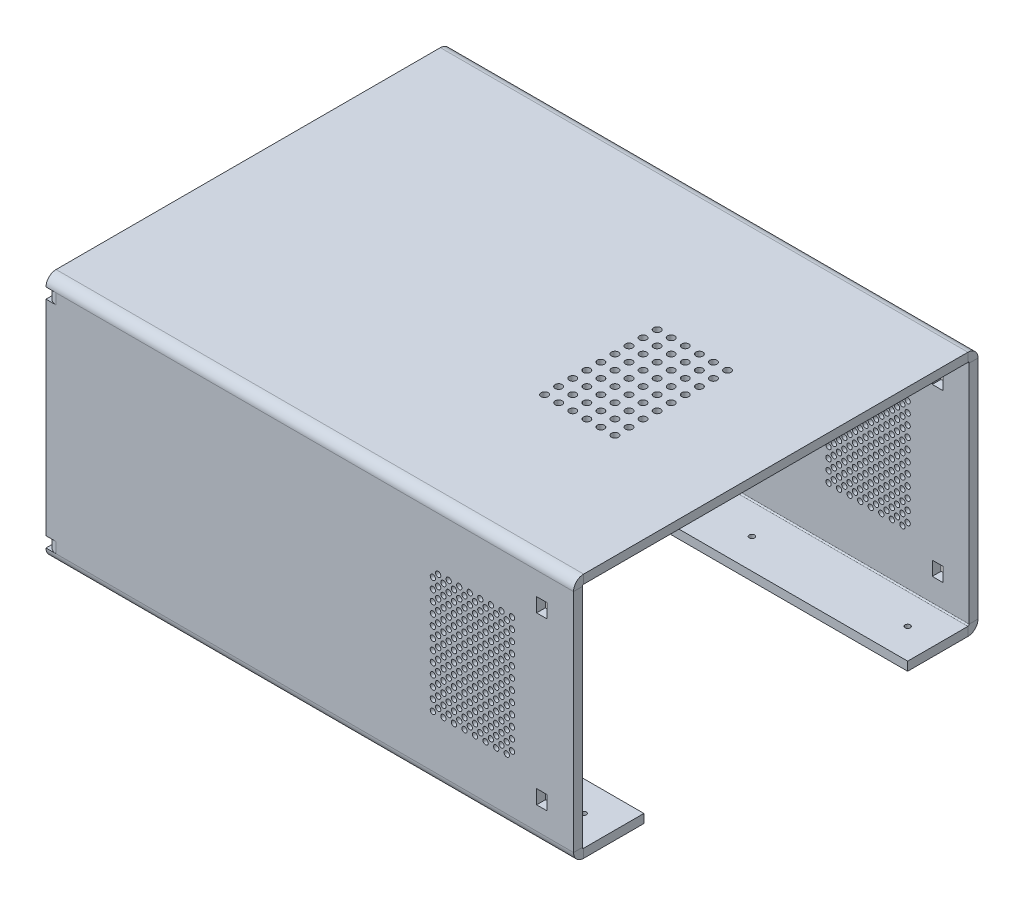
SolidWorks part; units mm, degrees
note: The reader was unsure of these and kept them because the rebuilt part matched: flange length of "Sides", "Bottom surfaces", "Edge-Flange4", "Edge-Flange5", "Edge-Flange6", "Edge-Flange7".
ref_plane "Front Plane" through (0, 0, 0) normal (0, 0, 1) x (1, 0, 0)
ref_plane "Top Plane" through (0, 0, 0) normal (0, 1, 0) x (1, 0, 0)
ref_plane "Right Plane" through (0, 0, 0) normal (1, 0, 0) x (0, 0, -1)
sketch "Sketch1" plane through (0, 0, 0) normal (0, 1, 0) x (1, 0, 0)
  line L1 (0, 0) -> (300, 0)
  line L2 (0, 0) -> (0, -220)
  line L3 (0, -220) -> (300, -220)
  line L4 (300, 0) -> (300, -220)
  dimension "D1" = 300
  dimension "D2" = 220
base flange "Top Surface" sketch "Sketch1" thickness 5 reverse thickness direction no parameters "D1"=0.7366
edge flange "Sides" sketch "Sketch10" flange profiles "Sketch10", "Sketch11" flange angle 90 flange length 140 flange position material outside bend radius 0.7366 thickness 5 relief rectangular parameters "D6"=10, "D8"=1
sketch "Sketch10" plane through (0, -5, 220) normal (0, 0, 1) x (-1, 0, 0)
  line L0 (0, 0) -> (-300, 0) construction
  line L1 (0, 0) -> (-300, 0)
  line L2 (-300, 0) -> (-300, 135)
  line L3 (-300, 135) -> (0, 135)
  line L4 (0, 135) -> (0, 0)
  dimension "D1" = 135
sketch "Sketch11" plane through (0, -5, 0) normal (0, 0, -1) x (1, 0, 0)
  line L0 (300, 0) -> (0, 0) construction
  line L1 (300, 0) -> (0, 0)
  line L2 (0, 0) -> (0, 135)
  line L3 (0, 135) -> (300, 135)
  line L4 (300, 135) -> (300, 0)
  line L7 (300, 135) -> (0, 135) construction
bend "EdgeBend1" bend radius 0.7366 bend angle 90 parameters "D5"=1
bend "EdgeBend2" bend radius 0.7366 bend angle 90 parameters "D5"=2
edge flange "Bottom surfaces" sketch "Sketch16" flange profiles "Sketch16", "Sketch17" flange angle 90 flange length 40 bend radius 0.7366 thickness 5 relief rectangular parameters "D6"=10, "D8"=1
sketch "Sketch16" plane through (0, -140, 220) normal (0, -1, 0) x (-1, 0, 0)
  line L2 (-300, 0) -> (-300, 35)
  line L3 (-300, 35) -> (0, 35)
  line L4 (0, 35) -> (0, 0)
  line L7 (0, 0) -> (-300, 0) construction
  line L8 (0, 0) -> (-300, 0)
sketch "Sketch17" plane through (0, -140, 0) normal (0, -1, 0) x (1, 0, 0)
  line L0 (300, 0) -> (0, 0) construction
  line L1 (300, 0) -> (0, 0)
  line L2 (0, 0) -> (0, 35)
  line L3 (0, 35) -> (300, 35)
  line L4 (300, 35) -> (300, 0)
bend "EdgeBend3" bend radius 0.7366 bend angle 90 parameters "D5"=3
bend "EdgeBend4" bend radius 0.7366 bend angle 90 parameters "D5"=4
sketch "Sketch27" plane through (0, -135, 0) normal (0, 1, 0) x (1, 0, 0)
  line L0 (17.1317, -17.8683) -> (17.1317, -202.1317) construction
  line L1 (17.1317, -202.1317) -> (105.7106, -202.1317) construction
  line L2 (105.7106, -202.1317) -> (194.2894, -202.1317) construction
  line L3 (194.2894, -202.1317) -> (282.8683, -202.1317) construction
  line L4 (282.8683, -202.1317) -> (282.8683, -17.8683) construction
  line L5 (282.8683, -17.8683) -> (194.2894, -17.8683) construction
  line L6 (194.2894, -17.8683) -> (105.7106, -17.8683) construction
  line L7 (105.7106, -17.8683) -> (105.7106, -202.1317) construction
  line L8 (17.1317, -17.8683) -> (105.7106, -17.8683) construction
  line L9 (194.2894, -17.8683) -> (194.2894, -202.1317) construction
  line L10 (17.1317, -17.8683) -> (0, -17.8683) construction
  line L11 (0, -35) -> (0, -0.7366) construction
  line L12 (282.8683, -17.8683) -> (300, -17.8683) construction
  line L13 (300, -0.7366) -> (300, -35) construction
  line L14 (17.1317, -17.8683) -> (17.1317, 5) construction
  line L15 (300, 5) -> (0, 5) construction
  line L16 (17.1317, -202.1317) -> (17.1317, -225) construction
  line L17 (0, -225) -> (300, -225) construction
  line L18 (17.1317, -202.1317) -> (0, -185) construction
  line L19 (17.1317, -202.1317) -> (0, -219.2634) construction
  line L20 (17.1317, -202.1317) -> (0, -202.1317) construction
  line L21 (0, -219.2634) -> (0, -185) construction
  line L22 (105.7106, -202.1317) -> (105.7106, -219.2634) construction
  line L23 (300, -219.2634) -> (0, -219.2634) construction
  circle A0 centre (17.1317, -17.8683) radius 1.5
  circle A1 centre (105.7106, -17.8683) radius 1.5
  circle A2 centre (194.2894, -17.8683) radius 1.5
  circle A3 centre (282.8683, -17.8683) radius 1.5
  circle A4 centre (17.1317, -202.1317) radius 1.5
  circle A5 centre (105.7106, -202.1317) radius 1.5
  circle A6 centre (194.2894, -202.1317) radius 1.5
  circle A7 centre (282.8683, -202.1317) radius 1.5
  dimension "D1" = 3
extrude "Screw Holes Bottom" cut sketch "Sketch27" against normal up to surface (5 mm away) normal cut yes up to face at (150, -140, 202.1317)
edge flange "Edge-Flange4" sketch "Sketch30" flange angle 90 flange length 11 flange position material inside bend radius 0.7366 thickness 5 relief none parameters "D6"=10
sketch "Sketch30" plane through (0, 0, 220) normal (-1, 0, 0) x (0, 1, 0)
  line L0 (-5.7366, 0) -> (-134.2634, 0) construction
  line L1 (-5.7366, 0) -> (-11.7366, 0)
  line L2 (-11.7366, 0) -> (-11.7366, 6)
  line L3 (-11.7366, 6) -> (-5.7366, 6)
  line L4 (-5.7366, 6) -> (-5.7366, 0)
  dimension "D1" = 6
  dimension "D2" = 6
bend "EdgeBend6" bend radius 0.7366 bend angle 90 parameters "D5"=5
edge flange "Edge-Flange5" sketch "Sketch33" flange angle 90 flange length 11 bend radius 0.7366 thickness 5 parameters "D6"=10
sketch "Sketch33" plane through (0, 0, 220) normal (-1, 0, 0) x (0, 1, 0)
  line L2 (-134.2634, 0) -> (-134.2634, 6)
  line L3 (-134.2634, 6) -> (-128.2634, 6)
  line L4 (-128.2634, 6) -> (-128.2634, 0)
  line L7 (-11.7366, 0) -> (-134.2634, 0) construction
  line L8 (-128.2634, 0) -> (-134.2634, 0)
  dimension "D1" = 6
  dimension "D2" = 6
bend "EdgeBend7" bend radius 0.7366 bend angle 90 parameters "D5"=6
edge flange "Edge-Flange6" sketch "Sketch36" flange angle 90 flange length 11 bend radius 0.7366 thickness 5 relief none parameters "D6"=10
sketch "Sketch36" plane through (0, 0, 0) normal (-1, 0, 0) x (0, -1, 0)
  line L0 (134.2634, 0) -> (5.7366, 0) construction
  line L1 (134.2634, 0) -> (128.2634, 0)
  line L2 (128.2634, 0) -> (128.2634, 6)
  line L3 (128.2634, 6) -> (134.2634, 6)
  line L4 (134.2634, 6) -> (134.2634, 0)
  dimension "D1" = 6
  dimension "D2" = 6
bend "EdgeBend8" bend radius 0.7366 bend angle 90 parameters "D5"=7
edge flange "Edge-Flange7" sketch "Sketch39" flange angle 90 flange length 11 bend radius 0.7366 thickness 5 relief none parameters "D6"=10
sketch "Sketch39" plane through (0, 0, 0) normal (-1, 0, 0) x (0, -1, 0)
  line L2 (5.7366, 0) -> (5.7366, 6)
  line L3 (5.7366, 6) -> (11.7366, 6)
  line L4 (11.7366, 6) -> (11.7366, 0)
  line L7 (128.2634, 0) -> (5.7366, 0) construction
  line L8 (11.7366, 0) -> (5.7366, 0)
  dimension "D1" = 6
  dimension "D2" = 6
bend "EdgeBend9" bend radius 0.7366 bend angle 90 parameters "D5"=8
sketch "Sketch40" plane through (0, 0, 0) normal (-1, 0, 0) x (0, 0, 1)
  line L0 (0.7366, -5.7366) -> (6, -11.7366) construction
  line L1 (6, -5.7366) -> (0.7366, -11.7366) construction
  line L4 (0.7366, -134.2634) -> (6, -128.2634) construction
  line L5 (0.7366, -128.2634) -> (6, -134.2634) construction
  line L6 (214, -128.2634) -> (219.2634, -134.2634) construction
  line L7 (219.2634, -128.2634) -> (214, -134.2634) construction
  line L8 (214, -134.2634) -> (219.2634, -134.2634) construction
  line L9 (214, -5.7366) -> (219.2634, -11.7366) construction
  line L10 (219.2634, -5.7366) -> (214, -11.7366) construction
  circle A0 centre (3.3683, -8.7366) radius 1.5
  circle A1 centre (3.3683, -131.2634) radius 1.5
  circle A2 centre (216.6317, -8.7366) radius 1.5
  circle A3 centre (216.6317, -131.2634) radius 1.5
  dimension "D1" = 3
extrude "Cut-Extrude3" cut sketch "Sketch40" against normal up to surface (5 mm away) normal cut yes up to face at (5, -8.7366, 3.3683)
sketch "Sketch42" plane through (0, 0, -5) normal (0, 0, -1) x (-1, 0, 0)
  line L0 (-265, -35.7366) -> (-265, -5.7366) construction
  line L1 (-300, -5.7366) -> (-5.7366, -5.7366) construction
  line L2 (-265, -35.7366) -> (-300, -35.7366) construction
  line L3 (-300, -5.7366) -> (-300, -134.2634) construction
  line L4 (-265, -35.7366) -> (-259, -35.7366) construction
  line L5 (-262, -38.7366) -> (-262, -35.7366) construction
  line L6 (-262, -38.7366) -> (-265, -35.7366) construction
  line L7 (-259, -35.7366) -> (-262, -38.7366) construction
  line L8 (-265, -41.7366) -> (-265, -11.7366) construction
  line L9 (-265, -53.7366) -> (-265, -23.7366) construction
  line L10 (-265, -53.7366) -> (-300, -53.7366) construction
  line L11 (-265, -53.7366) -> (-259, -53.7366) construction
  line L12 (-262, -56.7366) -> (-262, -53.7366) construction
  line L14 (-262, -56.7366) -> (-265, -53.7366) construction
  line L20 (-265, -47.7366) -> (-300, -47.7366) construction
  line L21 (-265, -41.7366) -> (-300, -41.7366) construction
  line L22 (-265, -47.7366) -> (-265, -17.7366) construction
  line L23 (-265, -41.7366) -> (-259, -41.7366) construction
  line L24 (-262, -44.7366) -> (-262, -41.7366) construction
  line L25 (-262, -44.7366) -> (-265, -41.7366) construction
  line L26 (-259, -41.7366) -> (-262, -44.7366) construction
  line L27 (-265, -47.7366) -> (-259, -47.7366) construction
  line L28 (-262, -50.7366) -> (-262, -47.7366) construction
  line L29 (-259, -47.7366) -> (-262, -50.7366) construction
  line L30 (-262, -50.7366) -> (-265, -47.7366) construction
  line L31 (-259, -53.7366) -> (-262, -56.7366) construction
  line L32 (-265, -59.7366) -> (-265, -29.7366) construction
  line L33 (-265, -59.7366) -> (-300, -59.7366) construction
  line L34 (-265, -59.7366) -> (-259, -59.7366) construction
  line L35 (-262, -62.7366) -> (-262, -59.7366) construction
  line L36 (-262, -62.7366) -> (-265, -59.7366) construction
  line L37 (-259, -59.7366) -> (-262, -62.7366) construction
  line L38 (-265, -65.7366) -> (-265, -35.7366) construction
  line L39 (-265, -65.7366) -> (-300, -65.7366) construction
  line L40 (-265, -65.7366) -> (-259, -65.7366) construction
  line L41 (-262, -68.7366) -> (-262, -65.7366) construction
  line L42 (-262, -68.7366) -> (-265, -65.7366) construction
  line L43 (-259, -65.7366) -> (-262, -68.7366) construction
  line L44 (-265, -71.7366) -> (-265, -41.7366) construction
  line L45 (-265, -71.7366) -> (-300, -71.7366) construction
  line L46 (-265, -71.7366) -> (-259, -71.7366) construction
  line L47 (-262, -74.7366) -> (-262, -71.7366) construction
  line L48 (-262, -74.7366) -> (-265, -71.7366) construction
  line L49 (-259, -71.7366) -> (-262, -74.7366) construction
  line L50 (-265, -77.7366) -> (-265, -47.7366) construction
  line L51 (-265, -77.7366) -> (-300, -77.7366) construction
  line L52 (-265, -77.7366) -> (-259, -77.7366) construction
  line L53 (-262, -80.7366) -> (-262, -77.7366) construction
  line L54 (-262, -80.7366) -> (-265, -77.7366) construction
  line L55 (-259, -77.7366) -> (-262, -80.7366) construction
  line L56 (-265, -83.7366) -> (-265, -53.7366) construction
  line L57 (-265, -83.7366) -> (-300, -83.7366) construction
  line L58 (-265, -83.7366) -> (-259, -83.7366) construction
  line L59 (-262, -86.7366) -> (-262, -83.7366) construction
  line L60 (-262, -86.7366) -> (-265, -83.7366) construction
  line L61 (-259, -83.7366) -> (-262, -86.7366) construction
  line L62 (-265, -89.7366) -> (-265, -59.7366) construction
  line L63 (-265, -89.7366) -> (-300, -89.7366) construction
  line L64 (-265, -89.7366) -> (-259, -89.7366) construction
  line L65 (-262, -92.7366) -> (-262, -89.7366) construction
  line L66 (-262, -92.7366) -> (-265, -89.7366) construction
  line L67 (-259, -89.7366) -> (-262, -92.7366) construction
  line L68 (-265, -95.7366) -> (-265, -65.7366) construction
  line L69 (-265, -95.7366) -> (-300, -95.7366) construction
  line L70 (-265, -95.7366) -> (-259, -95.7366) construction
  line L71 (-262, -98.7366) -> (-262, -95.7366) construction
  line L72 (-262, -98.7366) -> (-265, -95.7366) construction
  line L73 (-259, -95.7366) -> (-262, -98.7366) construction
  line L74 (-265, -101.7366) -> (-265, -71.7366) construction
  line L75 (-265, -101.7366) -> (-300, -101.7366) construction
  line L76 (-265, -101.7366) -> (-259, -101.7366) construction
  line L77 (-262, -104.7366) -> (-262, -101.7366) construction
  line L78 (-262, -104.7366) -> (-265, -101.7366) construction
  line L79 (-259, -101.7366) -> (-262, -104.7366) construction
  circle A0 centre (-265, -35.7366) radius 1.5
  circle A1 centre (-259, -35.7366) radius 1.5
  circle A2 centre (-253, -35.7366) radius 1.5
  circle A3 centre (-247, -35.7366) radius 1.5
  circle A4 centre (-241, -35.7366) radius 1.5
  circle A5 centre (-235, -35.7366) radius 1.5
  circle A6 centre (-229, -35.7366) radius 1.5
  circle A7 centre (-223, -35.7366) radius 1.5
  circle A16 centre (-262, -38.7366) radius 1.5
  circle A17 centre (-256, -38.7366) radius 1.5
  circle A18 centre (-250, -38.7366) radius 1.5
  circle A19 centre (-244, -38.7366) radius 1.5
  circle A20 centre (-238, -38.7366) radius 1.5
  circle A21 centre (-232, -38.7366) radius 1.5
  circle A22 centre (-226, -38.7366) radius 1.5
  circle A23 centre (-220, -38.7366) radius 1.5
  circle A24 centre (-265, -41.7366) radius 1.5
  circle A25 centre (-259, -41.7366) radius 1.5
  circle A26 centre (-253, -41.7366) radius 1.5
  circle A27 centre (-247, -41.7366) radius 1.5
  circle A28 centre (-241, -41.7366) radius 1.5
  circle A29 centre (-235, -41.7366) radius 1.5
  circle A30 centre (-229, -41.7366) radius 1.5
  circle A31 centre (-223, -41.7366) radius 1.5
  circle A32 centre (-262, -44.7366) radius 1.5
  circle A33 centre (-256, -44.7366) radius 1.5
  circle A34 centre (-250, -44.7366) radius 1.5
  circle A35 centre (-244, -44.7366) radius 1.5
  circle A36 centre (-238, -44.7366) radius 1.5
  circle A37 centre (-232, -44.7366) radius 1.5
  circle A38 centre (-226, -44.7366) radius 1.5
  circle A39 centre (-220, -44.7366) radius 1.5
  circle A40 centre (-265, -47.7366) radius 1.5
  circle A41 centre (-259, -47.7366) radius 1.5
  circle A42 centre (-253, -47.7366) radius 1.5
  circle A43 centre (-247, -47.7366) radius 1.5
  circle A44 centre (-241, -47.7366) radius 1.5
  circle A45 centre (-235, -47.7366) radius 1.5
  circle A46 centre (-229, -47.7366) radius 1.5
  circle A47 centre (-223, -47.7366) radius 1.5
  circle A48 centre (-262, -50.7366) radius 1.5
  circle A49 centre (-256, -50.7366) radius 1.5
  circle A50 centre (-250, -50.7366) radius 1.5
  circle A51 centre (-244, -50.7366) radius 1.5
  circle A52 centre (-238, -50.7366) radius 1.5
  circle A53 centre (-232, -50.7366) radius 1.5
  circle A54 centre (-226, -50.7366) radius 1.5
  circle A55 centre (-220, -50.7366) radius 1.5
  circle A56 centre (-265, -53.7366) radius 1.5
  circle A57 centre (-259, -53.7366) radius 1.5
  circle A58 centre (-253, -53.7366) radius 1.5
  circle A59 centre (-247, -53.7366) radius 1.5
  circle A60 centre (-241, -53.7366) radius 1.5
  circle A61 centre (-235, -53.7366) radius 1.5
  circle A62 centre (-229, -53.7366) radius 1.5
  circle A63 centre (-223, -53.7366) radius 1.5
  circle A64 centre (-262, -56.7366) radius 1.5
  circle A65 centre (-256, -56.7366) radius 1.5
  circle A66 centre (-250, -56.7366) radius 1.5
  circle A67 centre (-244, -56.7366) radius 1.5
  circle A68 centre (-238, -56.7366) radius 1.5
  circle A69 centre (-232, -56.7366) radius 1.5
  circle A70 centre (-226, -56.7366) radius 1.5
  circle A71 centre (-220, -56.7366) radius 1.5
  circle A72 centre (-265, -59.7366) radius 1.5
  circle A73 centre (-259, -59.7366) radius 1.5
  circle A74 centre (-253, -59.7366) radius 1.5
  circle A75 centre (-247, -59.7366) radius 1.5
  circle A76 centre (-241, -59.7366) radius 1.5
  circle A77 centre (-235, -59.7366) radius 1.5
  circle A78 centre (-229, -59.7366) radius 1.5
  circle A79 centre (-223, -59.7366) radius 1.5
  circle A80 centre (-262, -62.7366) radius 1.5
  circle A81 centre (-256, -62.7366) radius 1.5
  circle A82 centre (-250, -62.7366) radius 1.5
  circle A83 centre (-244, -62.7366) radius 1.5
  circle A84 centre (-238, -62.7366) radius 1.5
  circle A85 centre (-232, -62.7366) radius 1.5
  circle A86 centre (-226, -62.7366) radius 1.5
  circle A87 centre (-220, -62.7366) radius 1.5
  circle A88 centre (-265, -65.7366) radius 1.5
  circle A89 centre (-259, -65.7366) radius 1.5
  circle A90 centre (-253, -65.7366) radius 1.5
  circle A91 centre (-247, -65.7366) radius 1.5
  circle A92 centre (-241, -65.7366) radius 1.5
  circle A93 centre (-235, -65.7366) radius 1.5
  circle A94 centre (-229, -65.7366) radius 1.5
  circle A95 centre (-223, -65.7366) radius 1.5
  circle A96 centre (-262, -68.7366) radius 1.5
  circle A97 centre (-256, -68.7366) radius 1.5
  circle A98 centre (-250, -68.7366) radius 1.5
  circle A99 centre (-244, -68.7366) radius 1.5
  circle A100 centre (-238, -68.7366) radius 1.5
  circle A101 centre (-232, -68.7366) radius 1.5
  circle A102 centre (-226, -68.7366) radius 1.5
  circle A103 centre (-220, -68.7366) radius 1.5
  circle A104 centre (-265, -71.7366) radius 1.5
  circle A105 centre (-259, -71.7366) radius 1.5
  circle A106 centre (-253, -71.7366) radius 1.5
  circle A107 centre (-247, -71.7366) radius 1.5
  circle A108 centre (-241, -71.7366) radius 1.5
  circle A109 centre (-235, -71.7366) radius 1.5
  circle A110 centre (-229, -71.7366) radius 1.5
  circle A111 centre (-223, -71.7366) radius 1.5
  circle A112 centre (-262, -74.7366) radius 1.5
  circle A113 centre (-256, -74.7366) radius 1.5
  circle A114 centre (-250, -74.7366) radius 1.5
  circle A115 centre (-244, -74.7366) radius 1.5
  circle A116 centre (-238, -74.7366) radius 1.5
  circle A117 centre (-232, -74.7366) radius 1.5
  circle A118 centre (-226, -74.7366) radius 1.5
  circle A119 centre (-220, -74.7366) radius 1.5
  circle A120 centre (-265, -77.7366) radius 1.5
  circle A121 centre (-259, -77.7366) radius 1.5
  circle A122 centre (-253, -77.7366) radius 1.5
  circle A123 centre (-247, -77.7366) radius 1.5
  circle A124 centre (-241, -77.7366) radius 1.5
  circle A125 centre (-235, -77.7366) radius 1.5
  circle A126 centre (-229, -77.7366) radius 1.5
  circle A127 centre (-223, -77.7366) radius 1.5
  circle A128 centre (-262, -80.7366) radius 1.5
  circle A129 centre (-256, -80.7366) radius 1.5
  circle A130 centre (-250, -80.7366) radius 1.5
  circle A131 centre (-244, -80.7366) radius 1.5
  circle A132 centre (-238, -80.7366) radius 1.5
  circle A133 centre (-232, -80.7366) radius 1.5
  circle A134 centre (-226, -80.7366) radius 1.5
  circle A135 centre (-220, -80.7366) radius 1.5
  circle A136 centre (-265, -83.7366) radius 1.5
  circle A137 centre (-259, -83.7366) radius 1.5
  circle A138 centre (-253, -83.7366) radius 1.5
  circle A139 centre (-247, -83.7366) radius 1.5
  circle A140 centre (-241, -83.7366) radius 1.5
  circle A141 centre (-235, -83.7366) radius 1.5
  circle A142 centre (-229, -83.7366) radius 1.5
  circle A143 centre (-223, -83.7366) radius 1.5
  circle A144 centre (-262, -86.7366) radius 1.5
  circle A145 centre (-256, -86.7366) radius 1.5
  circle A146 centre (-250, -86.7366) radius 1.5
  circle A147 centre (-244, -86.7366) radius 1.5
  circle A148 centre (-238, -86.7366) radius 1.5
  circle A149 centre (-232, -86.7366) radius 1.5
  circle A150 centre (-226, -86.7366) radius 1.5
  circle A151 centre (-220, -86.7366) radius 1.5
  circle A152 centre (-265, -89.7366) radius 1.5
  circle A153 centre (-259, -89.7366) radius 1.5
  circle A154 centre (-253, -89.7366) radius 1.5
  circle A155 centre (-247, -89.7366) radius 1.5
  circle A156 centre (-241, -89.7366) radius 1.5
  circle A157 centre (-235, -89.7366) radius 1.5
  circle A158 centre (-229, -89.7366) radius 1.5
  circle A159 centre (-223, -89.7366) radius 1.5
  circle A160 centre (-262, -92.7366) radius 1.5
  circle A161 centre (-256, -92.7366) radius 1.5
  circle A162 centre (-250, -92.7366) radius 1.5
  circle A163 centre (-244, -92.7366) radius 1.5
  circle A164 centre (-238, -92.7366) radius 1.5
  circle A165 centre (-232, -92.7366) radius 1.5
  circle A166 centre (-226, -92.7366) radius 1.5
  circle A167 centre (-220, -92.7366) radius 1.5
  circle A168 centre (-265, -95.7366) radius 1.5
  circle A169 centre (-259, -95.7366) radius 1.5
  circle A170 centre (-253, -95.7366) radius 1.5
  circle A171 centre (-247, -95.7366) radius 1.5
  circle A172 centre (-241, -95.7366) radius 1.5
  circle A173 centre (-235, -95.7366) radius 1.5
  circle A174 centre (-229, -95.7366) radius 1.5
  circle A175 centre (-223, -95.7366) radius 1.5
  circle A176 centre (-262, -98.7366) radius 1.5
  circle A177 centre (-256, -98.7366) radius 1.5
  circle A178 centre (-250, -98.7366) radius 1.5
  circle A179 centre (-244, -98.7366) radius 1.5
  circle A180 centre (-238, -98.7366) radius 1.5
  circle A181 centre (-232, -98.7366) radius 1.5
  circle A182 centre (-226, -98.7366) radius 1.5
  circle A183 centre (-220, -98.7366) radius 1.5
  circle A184 centre (-265, -101.7366) radius 1.5
  circle A185 centre (-259, -101.7366) radius 1.5
  circle A186 centre (-253, -101.7366) radius 1.5
  circle A187 centre (-247, -101.7366) radius 1.5
  circle A188 centre (-241, -101.7366) radius 1.5
  circle A189 centre (-235, -101.7366) radius 1.5
  circle A190 centre (-229, -101.7366) radius 1.5
  circle A191 centre (-223, -101.7366) radius 1.5
  circle A192 centre (-262, -104.7366) radius 1.5
  circle A193 centre (-256, -104.7366) radius 1.5
  circle A194 centre (-250, -104.7366) radius 1.5
  circle A195 centre (-244, -104.7366) radius 1.5
  circle A196 centre (-238, -104.7366) radius 1.5
  circle A197 centre (-232, -104.7366) radius 1.5
  circle A198 centre (-226, -104.7366) radius 1.5
  circle A199 centre (-220, -104.7366) radius 1.5
  dimension "D1" = 3
  dimension "D5" = 3
  dimension "D6" = 3
  dimension "D2" = 35
  dimension "D3" = 30
  dimension "D7" = 8
  dimension "D4" = 8
  dimension "D8" = 12
extrude "Side Air Vents" cut sketch "Sketch42" against normal through all normal cut yes
sketch "Sketch46" plane through (0, 0, 0) normal (0, 1, 0) x (1, 0, 0)
  line L0 (200.5373, -110) -> (200.5373, -0.7366) construction
  line L1 (300, -0.7366) -> (0, -0.7366) construction
  line L2 (200.5373, -110) -> (200.5373, -219.2634) construction
  line L3 (0, -219.2634) -> (300, -219.2634) construction
  circle A4 centre (200.5373, -78) radius 2
  circle A8 centre (200.5373, -86) radius 2
  circle A12 centre (200.5373, -94) radius 2
  circle A16 centre (200.5373, -102) radius 2
  circle A20 centre (200.5373, -110) radius 2
  circle A21 centre (200.5373, -118) radius 2
  circle A22 centre (200.5373, -126) radius 2
  circle A23 centre (200.5373, -134) radius 2
  circle A24 centre (200.5373, -142) radius 2
  circle A25 centre (208.5373, -78) radius 2
  circle A26 centre (208.5373, -86) radius 2
  circle A27 centre (208.5373, -94) radius 2
  circle A28 centre (208.5373, -102) radius 2
  circle A29 centre (208.5373, -110) radius 2
  circle A30 centre (208.5373, -118) radius 2
  circle A31 centre (208.5373, -126) radius 2
  circle A32 centre (208.5373, -134) radius 2
  circle A33 centre (208.5373, -142) radius 2
  circle A34 centre (216.5373, -78) radius 2
  circle A35 centre (216.5373, -86) radius 2
  circle A36 centre (216.5373, -94) radius 2
  circle A37 centre (216.5373, -102) radius 2
  circle A38 centre (216.5373, -110) radius 2
  circle A39 centre (216.5373, -118) radius 2
  circle A40 centre (216.5373, -126) radius 2
  circle A41 centre (216.5373, -134) radius 2
  circle A42 centre (216.5373, -142) radius 2
  circle A43 centre (224.5373, -78) radius 2
  circle A44 centre (224.5373, -86) radius 2
  circle A45 centre (224.5373, -94) radius 2
  circle A46 centre (224.5373, -102) radius 2
  circle A47 centre (224.5373, -110) radius 2
  circle A48 centre (224.5373, -118) radius 2
  circle A49 centre (224.5373, -126) radius 2
  circle A50 centre (224.5373, -134) radius 2
  circle A51 centre (224.5373, -142) radius 2
  circle A52 centre (232.5373, -78) radius 2
  circle A53 centre (232.5373, -86) radius 2
  circle A54 centre (232.5373, -94) radius 2
  circle A55 centre (232.5373, -102) radius 2
  circle A56 centre (232.5373, -110) radius 2
  circle A57 centre (232.5373, -118) radius 2
  circle A58 centre (232.5373, -126) radius 2
  circle A59 centre (232.5373, -134) radius 2
  circle A60 centre (232.5373, -142) radius 2
  circle A61 centre (240.5373, -78) radius 2
  circle A62 centre (240.5373, -86) radius 2
  circle A63 centre (240.5373, -94) radius 2
  circle A64 centre (240.5373, -102) radius 2
  circle A65 centre (240.5373, -110) radius 2
  circle A66 centre (240.5373, -118) radius 2
  circle A67 centre (240.5373, -126) radius 2
  circle A68 centre (240.5373, -134) radius 2
  circle A69 centre (240.5373, -142) radius 2
  dimension "D1" = 6
extrude "Top Air Vents" cut sketch "Sketch46" against normal up to surface (5 mm away) normal cut yes up to face at (150, -5, 110)
sketch "Sketch43" plane through (0, 0, 225) normal (0, 0, 1) x (1, 0, 0)
  line L0 (279, -18.7366) -> (279, -5.7366) construction
  line L1 (279, -18.7366) -> (285, -18.7366)
  line L2 (279, -18.7366) -> (279, -26.7366)
  line L3 (279, -26.7366) -> (285, -26.7366)
  line L4 (285, -18.7366) -> (285, -26.7366)
  line L5 (279, -113.2634) -> (285, -113.2634)
  line L6 (279, -113.2634) -> (279, -121.2634)
  line L7 (279, -121.2634) -> (285, -121.2634)
  line L8 (285, -113.2634) -> (285, -121.2634)
  line L9 (5.7366, -5.7366) -> (300, -5.7366) construction
  line L10 (279, -121.2634) -> (279, -134.2634) construction
  line L11 (5.7366, -134.2634) -> (300, -134.2634) construction
  line L12 (300, -134.2634) -> (300, -5.7366) construction
  dimension "D1" = 6
  dimension "D2" = 8
  dimension "D3" = 13
  dimension "D4" = 15
extrude "Snap Hook Groves" cut sketch "Sketch43" against normal up to surface (230 mm away) normal cut yes up to face at (265, -82.2366, -5)
sketch "Bend-Lines1" [suppressed] plane through (0, 0, 0) normal (0, 1, 0) x (1, 0, 0)
sketch "Bounding-Box1" [suppressed] plane through (0, 0, 0) normal (0, 1, 0) x (1, 0, 0)
sheet metal parameters "Sheet-Metal1" thickness 5 parameters "D1"=0.7366
flat pattern "Flat-Pattern1" [suppressed]
sketch "Bend-Lines2" plane through (0, 0, 0) normal (0, 1, 0) x (1, 0, 0)
sketch3d "Bounding-Box2" [suppressed]
  line L0 (-300, -250, 0) -> (0, -250, 0) construction
  line L1 (-300, 0, 0) -> (0, 0, 0) construction
  line L2 (-300, -250, 0) -> (-300, 0, 0) construction
  line L3 (0, -250, 0) -> (0, 0, 0) construction
sheet metal parameters "Sheet-Metal2" thickness 5 parameters "D1"=0.7366
flat pattern "Flat-Pattern1" [suppressed]
sketch "Bend-Lines2" plane through (0, 0, 0) normal (0, 1, 0) x (1, 0, 0)
  line L0 (300, 1.8054) -> (0, 1.8054) construction
  line L1 (0, -251.8054) -> (300, -251.8054) construction
  line L2 (300, 1.8054) -> (0, 1.8054) construction
  line L3 (0, -251.8054) -> (300, -251.8054) construction
sketch3d "Bounding-Box2" [suppressed]
  line L0 (0, 98.6108, 0) -> (0, -348.6108, 0) construction
  line L1 (300, 98.6108, 0) -> (300, -348.6108, 0) construction
  line L2 (0, 98.6108, 0) -> (300, 98.6108, 0) construction
  line L3 (0, -348.6108, 0) -> (300, -348.6108, 0) construction
bend of the flat pattern "Flatten-<EdgeBend1>1"
bend of the flat pattern "Flatten-<EdgeBend2>1"
sheet metal parameters "Sheet-Metal3" thickness 5 parameters "D1"=0.7366
flat pattern "Flat-Pattern1" [suppressed]
sketch "Bend-Lines2" plane through (0, 0, 0) normal (0, 1, 0) x (1, 0, 0)
  line L0 (300, 1.8054) -> (0, 1.8054) construction
  line L1 (0, -251.8054) -> (300, -251.8054) construction
  line L2 (300, 1.8054) -> (0, 1.8054) construction
  line L3 (0, -251.8054) -> (300, -251.8054) construction
  line L4 (300, 100.4163) -> (0, 100.4163) construction
  line L5 (0, -350.4163) -> (300, -350.4163) construction
  line L6 (300, 100.4163) -> (0, 100.4163) construction
  line L7 (0, -350.4163) -> (300, -350.4163) construction
sketch3d "Bounding-Box2" [suppressed]
  line L0 (0, 137.2217, 0) -> (0, -387.2217, 0) construction
  line L1 (300, 137.2217, 0) -> (300, -387.2217, 0) construction
  line L2 (0, 137.2217, 0) -> (300, 137.2217, 0) construction
  line L3 (0, -387.2217, 0) -> (300, -387.2217, 0) construction
bend of the flat pattern "Flatten-<EdgeBend3>1"
bend of the flat pattern "Flatten-<EdgeBend4>1"
bend of the flat pattern "Flatten-<EdgeBend1>1"
bend of the flat pattern "Flatten-<EdgeBend2>1"
sheet metal parameters "Sheet-Metal7" thickness 5 parameters "D1"=0.7366
flat pattern "Flat-Pattern1" [suppressed]
sketch "Bend-Lines2" plane through (0, 0, 0) normal (0, 1, 0) x (1, 0, 0)
  line L0 (300, 1.8054) -> (0, 1.8054) construction
  line L1 (0, -251.8054) -> (300, -251.8054) construction
  line L2 (300, 1.8054) -> (0, 1.8054) construction
  line L3 (0, -251.8054) -> (300, -251.8054) construction
  line L4 (300, 100.4163) -> (0, 100.4163) construction
  line L5 (0, -350.4163) -> (300, -350.4163) construction
  line L6 (300, 100.4163) -> (0, 100.4163) construction
  line L7 (0, -350.4163) -> (300, -350.4163) construction
sketch3d "Bounding-Box2" [suppressed]
  line L0 (0, 137.2217, 0) -> (0, -387.2217, 0) construction
  line L1 (300, 137.2217, 0) -> (300, -387.2217, 0) construction
  line L2 (0, 137.2217, 0) -> (300, 137.2217, 0) construction
  line L3 (0, -387.2217, 0) -> (300, -387.2217, 0) construction
bend of the flat pattern "Flatten-<EdgeBend3>1"
bend of the flat pattern "Flatten-<EdgeBend4>1"
bend of the flat pattern "Flatten-<EdgeBend1>1"
bend of the flat pattern "Flatten-<EdgeBend2>1"
sheet metal parameters "Sheet-Metal8" thickness 5 parameters "D1"=0.7366
flat pattern "Flat-Pattern1" [suppressed]
sketch "Bend-Lines2" plane through (0, 0, 0) normal (0, 1, 0) x (1, 0, 0)
  line L0 (300, 1.8054) -> (0, 1.8054) construction
  line L1 (0, -251.8054) -> (300, -251.8054) construction
  line L2 (300, 1.8054) -> (0, 1.8054) construction
  line L3 (0, -251.8054) -> (300, -251.8054) construction
  line L4 (300, 100.4163) -> (0, 100.4163) construction
  line L5 (0, -350.4163) -> (300, -350.4163) construction
  line L6 (300, 100.4163) -> (0, 100.4163) construction
  line L7 (0, -350.4163) -> (300, -350.4163) construction
  line L8 (3.1946, -260.3474) -> (3.1946, -254.3474) construction
  line L9 (3.1946, -260.3474) -> (3.1946, -254.3474) construction
sketch3d "Bounding-Box2" [suppressed]
  line L0 (300.0004, 137.2214, 0) -> (300, -387.2217, 0) construction
  line L1 (-4.6105, 137.2217, 0) -> (-4.6109, -387.2214, 0) construction
  line L2 (300.0004, 137.2214, 0) -> (-4.6105, 137.2217, 0) construction
  line L3 (300, -387.2217, 0) -> (-4.6109, -387.2214, 0) construction
bend of the flat pattern "Flatten-<EdgeBend6>1"
bend of the flat pattern "Flatten-<EdgeBend3>1"
bend of the flat pattern "Flatten-<EdgeBend4>1"
bend of the flat pattern "Flatten-<EdgeBend1>1"
bend of the flat pattern "Flatten-<EdgeBend2>1"
sheet metal parameters "Sheet-Metal9" thickness 5 parameters "D1"=0.7366
flat pattern "Flat-Pattern1" [suppressed]
sketch "Bend-Lines2" plane through (0, 0, 0) normal (0, 1, 0) x (1, 0, 0)
  line L0 (300, 1.8054) -> (0, 1.8054) construction
  line L1 (0, -251.8054) -> (300, -251.8054) construction
  line L2 (300, 1.8054) -> (0, 1.8054) construction
  line L3 (0, -251.8054) -> (300, -251.8054) construction
  line L4 (300, 100.4163) -> (0, 100.4163) construction
  line L5 (0, -350.4163) -> (300, -350.4163) construction
  line L6 (300, 100.4163) -> (0, 100.4163) construction
  line L7 (0, -350.4163) -> (300, -350.4163) construction
  line L8 (3.1946, -260.3474) -> (3.1946, -254.3474) construction
  line L9 (3.1946, -260.3474) -> (3.1946, -254.3474) construction
  line L10 (3.1946, -347.8742) -> (3.1946, -341.8742) construction
  line L11 (3.1946, -347.8742) -> (3.1946, -341.8742) construction
sketch3d "Bounding-Box2" [suppressed]
  line L0 (300.0004, 137.2214, 0) -> (300, -387.2217, 0) construction
  line L1 (-4.6104, 137.2217, 0) -> (-4.6109, -387.2214, 0) construction
  line L2 (300.0004, 137.2214, 0) -> (-4.6104, 137.2217, 0) construction
  line L3 (300, -387.2217, 0) -> (-4.6109, -387.2214, 0) construction
bend of the flat pattern "Flatten-<EdgeBend6>1"
bend of the flat pattern "Flatten-<EdgeBend7>1"
bend of the flat pattern "Flatten-<EdgeBend3>1"
bend of the flat pattern "Flatten-<EdgeBend4>1"
bend of the flat pattern "Flatten-<EdgeBend1>1"
bend of the flat pattern "Flatten-<EdgeBend2>1"
sheet metal parameters "Sheet-Metal10" thickness 5 parameters "D1"=0.7366
flat pattern "Flat-Pattern1" [suppressed]
sketch "Bend-Lines2" plane through (0, 0, 0) normal (0, 1, 0) x (1, 0, 0)
  line L0 (300, 1.8054) -> (0, 1.8054) construction
  line L1 (0, -251.8054) -> (300, -251.8054) construction
  line L2 (300, 1.8054) -> (0, 1.8054) construction
  line L3 (0, -251.8054) -> (300, -251.8054) construction
  line L4 (300, 100.4163) -> (0, 100.4163) construction
  line L5 (0, -350.4163) -> (300, -350.4163) construction
  line L6 (300, 100.4163) -> (0, 100.4163) construction
  line L7 (0, -350.4163) -> (300, -350.4163) construction
  line L8 (3.1946, -260.3474) -> (3.1946, -254.3474) construction
  line L9 (3.1946, -260.3474) -> (3.1946, -254.3474) construction
  line L10 (3.1946, -347.8742) -> (3.1946, -341.8742) construction
  line L11 (3.1946, -347.8742) -> (3.1946, -341.8742) construction
  line L12 (3.1946, 91.8742) -> (3.1946, 97.8742) construction
  line L13 (3.1946, 91.8742) -> (3.1946, 97.8742) construction
sketch3d "Bounding-Box2" [suppressed]
  line L0 (-4.6108, 137.2217, 0) -> (-4.6108, -387.2217, 0) construction
  line L1 (300, 137.2217, 0) -> (300, -387.2217, 0) construction
  line L2 (-4.6108, 137.2217, 0) -> (300, 137.2217, 0) construction
  line L3 (-4.6108, -387.2217, 0) -> (300, -387.2217, 0) construction
bend of the flat pattern "Flatten-<EdgeBend6>1"
bend of the flat pattern "Flatten-<EdgeBend7>1"
bend of the flat pattern "Flatten-<EdgeBend8>1"
bend of the flat pattern "Flatten-<EdgeBend3>1"
bend of the flat pattern "Flatten-<EdgeBend4>1"
bend of the flat pattern "Flatten-<EdgeBend1>1"
bend of the flat pattern "Flatten-<EdgeBend2>1"
sheet metal parameters "Sheet-Metal11" thickness 5 parameters "D1"=0.7366
flat pattern "Flat-Pattern1" [suppressed]
sketch "Bend-Lines2" plane through (0, 0, 0) normal (0, 1, 0) x (1, 0, 0)
  line L0 (300, 1.8054) -> (0, 1.8054) construction
  line L1 (0, -251.8054) -> (300, -251.8054) construction
  line L2 (300, 1.8054) -> (0, 1.8054) construction
  line L3 (0, -251.8054) -> (300, -251.8054) construction
  line L4 (300, 100.4163) -> (0, 100.4163) construction
  line L5 (0, -350.4163) -> (300, -350.4163) construction
  line L6 (300, 100.4163) -> (0, 100.4163) construction
  line L7 (0, -350.4163) -> (300, -350.4163) construction
  line L8 (3.1946, -260.3474) -> (3.1946, -254.3474) construction
  line L9 (3.1946, -260.3474) -> (3.1946, -254.3474) construction
  line L10 (3.1946, -347.8742) -> (3.1946, -341.8742) construction
  line L11 (3.1946, -347.8742) -> (3.1946, -341.8742) construction
  line L12 (3.1946, 91.8742) -> (3.1946, 97.8742) construction
  line L13 (3.1946, 91.8742) -> (3.1946, 97.8742) construction
  line L14 (3.1946, 4.3474) -> (3.1946, 10.3474) construction
  line L15 (3.1946, 4.3474) -> (3.1946, 10.3474) construction
sketch3d "Bounding-Box2" [suppressed]
  line L0 (-4.6108, 137.2217, 0) -> (-4.6108, -387.2217, 0) construction
  line L1 (300, 137.2217, 0) -> (300, -387.2217, 0) construction
  line L2 (-4.6108, 137.2217, 0) -> (300, 137.2217, 0) construction
  line L3 (-4.6108, -387.2217, 0) -> (300, -387.2217, 0) construction
bend of the flat pattern "Flatten-<EdgeBend6>1"
bend of the flat pattern "Flatten-<EdgeBend7>1"
bend of the flat pattern "Flatten-<EdgeBend8>1"
bend of the flat pattern "Flatten-<EdgeBend9>1"
bend of the flat pattern "Flatten-<EdgeBend3>1"
bend of the flat pattern "Flatten-<EdgeBend4>1"
bend of the flat pattern "Flatten-<EdgeBend1>1"
bend of the flat pattern "Flatten-<EdgeBend2>1"
sheet metal parameters "Sheet-Metal12" thickness 5 parameters "D1"=0.7366
flat pattern "Flat-Pattern1" [suppressed]
sketch "Bend-Lines2" plane through (0, 0, 0) normal (0, 1, 0) x (1, 0, 0)
  line L0 (300, 1.8054) -> (0, 1.8054) construction
  line L1 (0, -251.8054) -> (300, -251.8054) construction
  line L2 (300, 1.8054) -> (0, 1.8054) construction
  line L3 (0, -251.8054) -> (300, -251.8054) construction
  line L4 (300, 100.4163) -> (0, 100.4163) construction
  line L5 (0, -350.4163) -> (300, -350.4163) construction
  line L6 (300, 100.4163) -> (0, 100.4163) construction
  line L7 (0, -350.4163) -> (300, -350.4163) construction
  line L8 (3.1946, -260.3474) -> (3.1946, -254.3474) construction
  line L9 (3.1946, -260.3474) -> (3.1946, -254.3474) construction
  line L10 (3.1946, -347.8742) -> (3.1946, -341.8742) construction
  line L11 (3.1946, -347.8742) -> (3.1946, -341.8742) construction
  line L12 (3.1946, 91.8742) -> (3.1946, 97.8742) construction
  line L13 (3.1946, 91.8742) -> (3.1946, 97.8742) construction
  line L14 (3.1946, 4.3474) -> (3.1946, 10.3474) construction
  line L15 (3.1946, 4.3474) -> (3.1946, 10.3474) construction
sketch3d "Bounding-Box2" [suppressed]
  line L0 (-4.6108, 137.2217, 0) -> (-4.6108, -387.2217, 0) construction
  line L1 (300, 137.2217, 0) -> (300, -387.2217, 0) construction
  line L2 (-4.6108, 137.2217, 0) -> (300, 137.2217, 0) construction
  line L3 (-4.6108, -387.2217, 0) -> (300, -387.2217, 0) construction
bend of the flat pattern "Flatten-<EdgeBend6>1"
bend of the flat pattern "Flatten-<EdgeBend7>1"
bend of the flat pattern "Flatten-<EdgeBend8>1"
bend of the flat pattern "Flatten-<EdgeBend9>1"
bend of the flat pattern "Flatten-<EdgeBend3>1"
bend of the flat pattern "Flatten-<EdgeBend4>1"
bend of the flat pattern "Flatten-<EdgeBend1>1"
bend of the flat pattern "Flatten-<EdgeBend2>1"
sheet metal parameters "Sheet-Metal14" thickness 5 parameters "D1"=0.7366
flat pattern "Flat-Pattern1" [suppressed]
sketch "Bend-Lines2" plane through (0, 0, 0) normal (0, 1, 0) x (1, 0, 0)
  line L0 (300, 1.8054) -> (0, 1.8054) construction
  line L1 (0, -251.8054) -> (300, -251.8054) construction
  line L2 (300, 1.8054) -> (0, 1.8054) construction
  line L3 (0, -251.8054) -> (300, -251.8054) construction
  line L4 (300, 100.4163) -> (0, 100.4163) construction
  line L5 (0, -350.4163) -> (300, -350.4163) construction
  line L6 (300, 100.4163) -> (0, 100.4163) construction
  line L7 (0, -350.4163) -> (300, -350.4163) construction
  line L8 (3.1946, -260.3474) -> (3.1946, -254.3474) construction
  line L9 (3.1946, -260.3474) -> (3.1946, -254.3474) construction
  line L10 (3.1946, -347.8742) -> (3.1946, -341.8742) construction
  line L11 (3.1946, -347.8742) -> (3.1946, -341.8742) construction
  line L12 (3.1946, 91.8742) -> (3.1946, 97.8742) construction
  line L13 (3.1946, 91.8742) -> (3.1946, 97.8742) construction
  line L14 (3.1946, 4.3474) -> (3.1946, 10.3474) construction
  line L15 (3.1946, 4.3474) -> (3.1946, 10.3474) construction
sketch3d "Bounding-Box2" [suppressed]
  line L0 (-4.6108, 137.2217, 0) -> (-4.6108, -387.2217, 0) construction
  line L1 (300, 137.2217, 0) -> (300, -387.2217, 0) construction
  line L2 (-4.6108, 137.2217, 0) -> (300, 137.2217, 0) construction
  line L3 (-4.6108, -387.2217, 0) -> (300, -387.2217, 0) construction
bend of the flat pattern "Flatten-<EdgeBend6>1"
bend of the flat pattern "Flatten-<EdgeBend7>1"
bend of the flat pattern "Flatten-<EdgeBend8>1"
bend of the flat pattern "Flatten-<EdgeBend9>1"
bend of the flat pattern "Flatten-<EdgeBend3>1"
bend of the flat pattern "Flatten-<EdgeBend4>1"
bend of the flat pattern "Flatten-<EdgeBend1>1"
bend of the flat pattern "Flatten-<EdgeBend2>1"
sheet metal parameters "Sheet-Metal20" thickness 5 parameters "D1"=0.7366
flat pattern "Flat-Pattern1"
sketch "Bend-Lines2" plane through (0, 0, 0) normal (0, 1, 0) x (1, 0, 0)
  line L0 (300, 1.8054) -> (0, 1.8054) construction
  line L1 (0, -221.8054) -> (300, -221.8054) construction
  line L2 (300, 1.8054) -> (0, 1.8054) construction
  line L3 (0, -221.8054) -> (300, -221.8054) construction
  line L4 (300, 135.4163) -> (0, 135.4163) construction
  line L5 (0, -355.4163) -> (300, -355.4163) construction
  line L6 (300, 135.4163) -> (0, 135.4163) construction
  line L7 (0, -355.4163) -> (300, -355.4163) construction
  line L8 (3.1946, -224.3474) -> (3.1946, -230.3474) construction
  line L9 (3.1946, -224.3474) -> (3.1946, -230.3474) construction
  line L10 (3.1946, -352.8742) -> (3.1946, -346.8742) construction
  line L11 (3.1946, -352.8742) -> (3.1946, -346.8742) construction
  line L12 (3.1946, 126.8742) -> (3.1946, 132.8742) construction
  line L13 (3.1946, 126.8742) -> (3.1946, 132.8742) construction
  line L14 (3.1946, 4.3474) -> (3.1946, 10.3474) construction
  line L15 (3.1946, 4.3474) -> (3.1946, 10.3474) construction
sketch3d "Bounding-Box2" [suppressed]
  line L0 (-4.6108, 172.2217, 0) -> (-4.6108, -392.2217, 0) construction
  line L1 (300, 172.2217, 0) -> (300, -392.2217, 0) construction
  line L2 (-4.6108, 172.2217, 0) -> (300, 172.2217, 0) construction
  line L3 (-4.6108, -392.2217, 0) -> (300, -392.2217, 0) construction
bend of the flat pattern "Flatten-<EdgeBend6>1"
bend of the flat pattern "Flatten-<EdgeBend7>1"
bend of the flat pattern "Flatten-<EdgeBend8>1"
bend of the flat pattern "Flatten-<EdgeBend9>1"
bend of the flat pattern "Flatten-<EdgeBend3>1"
bend of the flat pattern "Flatten-<EdgeBend4>1"
bend of the flat pattern "Flatten-<EdgeBend1>1"
bend of the flat pattern "Flatten-<EdgeBend2>1"
sheet metal parameters "Sheet-Metal21" thickness 5 parameters "D1"=0.7366
flat pattern "Flat-Pattern1"
sketch "Bend-Lines2" plane through (0, 0, 0) normal (0, 1, 0) x (1, 0, 0)
  line L0 (300, 1.8054) -> (0, 1.8054) construction
  line L1 (0, -221.8054) -> (300, -221.8054) construction
  line L2 (300, 1.8054) -> (0, 1.8054) construction
  line L3 (0, -221.8054) -> (300, -221.8054) construction
  line L4 (300, 135.4163) -> (0, 135.4163) construction
  line L5 (0, -355.4163) -> (300, -355.4163) construction
  line L6 (300, 135.4163) -> (0, 135.4163) construction
  line L7 (0, -355.4163) -> (300, -355.4163) construction
  line L8 (3.1946, -224.3474) -> (3.1946, -230.3474) construction
  line L9 (3.1946, -224.3474) -> (3.1946, -230.3474) construction
  line L10 (3.1946, -352.8742) -> (3.1946, -346.8742) construction
  line L11 (3.1946, -352.8742) -> (3.1946, -346.8742) construction
  line L12 (3.1946, 126.8742) -> (3.1946, 132.8742) construction
  line L13 (3.1946, 126.8742) -> (3.1946, 132.8742) construction
  line L14 (3.1946, 4.3474) -> (3.1946, 10.3474) construction
  line L15 (3.1946, 4.3474) -> (3.1946, 10.3474) construction
sketch3d "Bounding-Box2" [suppressed]
  line L0 (-4.6108, 172.2217, 0) -> (-4.6108, -392.2217, 0) construction
  line L1 (300, 172.2217, 0) -> (300, -392.2217, 0) construction
  line L2 (-4.6108, 172.2217, 0) -> (300, 172.2217, 0) construction
  line L3 (-4.6108, -392.2217, 0) -> (300, -392.2217, 0) construction
bend of the flat pattern "Flatten-<EdgeBend6>1"
bend of the flat pattern "Flatten-<EdgeBend7>1"
bend of the flat pattern "Flatten-<EdgeBend8>1"
bend of the flat pattern "Flatten-<EdgeBend9>1"
bend of the flat pattern "Flatten-<EdgeBend3>1"
bend of the flat pattern "Flatten-<EdgeBend4>1"
bend of the flat pattern "Flatten-<EdgeBend1>1"
bend of the flat pattern "Flatten-<EdgeBend2>1"
